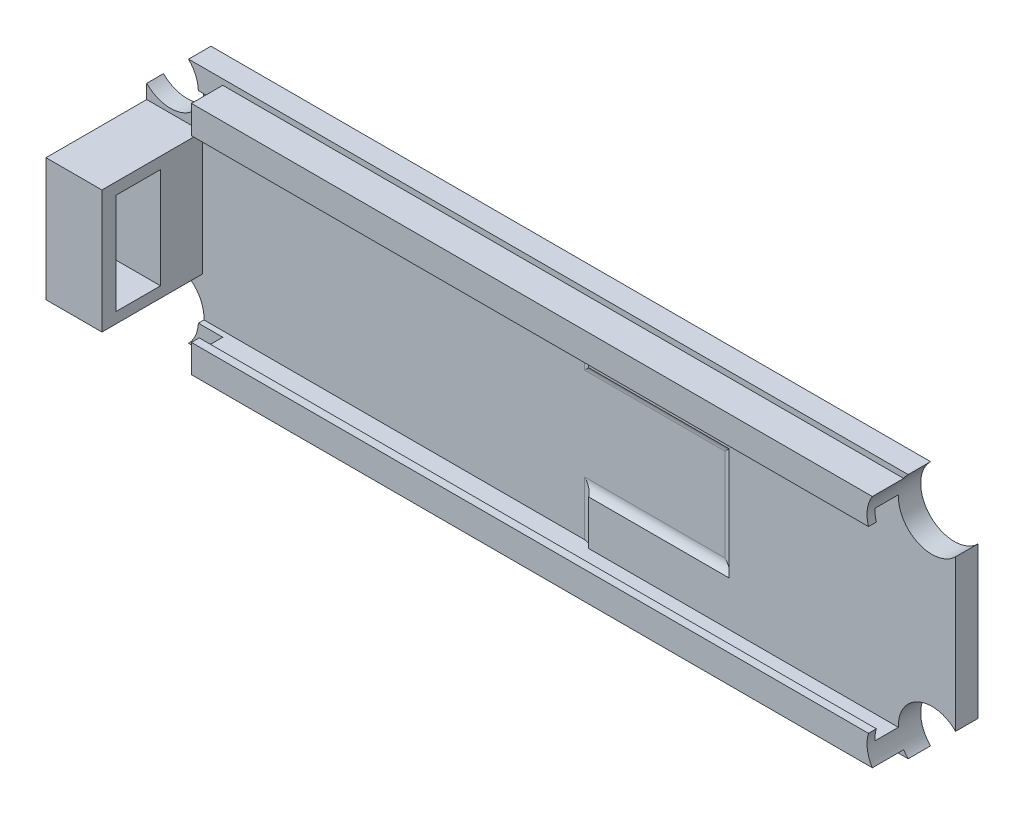
SolidWorks part; units mm, degrees
ref_plane "Ebene vorne" through (0, 0, 0) normal (1, 0, 0) x (0, 1, 0)
ref_plane "Ebene oben" through (0, 0, 0) normal (0, 0, 1) x (0, 1, 0)
ref_plane "Ebene rechts" through (0, 0, 0) normal (0, 1, 0) x (-1, 0, 0)
sketch "Skizze1" plane through (0, 0, 0) normal (0, 0, 1) x (0, 1, 0)
  line L30 (-11, -36.4) -> (11, -36.4)
  line L31 (-11, -36.4) -> (-11, 36.4)
  line L32 (-11, 36.4) -> (11, 36.4)
  line L33 (11, -36.4) -> (11, 36.4)
  line L34 (-11, -36.4) -> (11, 36.4) construction
  line L35 (-11, 36.4) -> (11, -36.4) construction
  point P0 (0, 0)
  dimension "D1" = 22
  dimension "D2" = 72.8
extrude "Aufsatz-Linear austragen1" add sketch "Skizze1" along normal blind 2
sketch "Skizze2" plane through (0, 0, 2) normal (0, 0, 1) x (1, 0, 0)
  line L0 (36.4, 11) -> (-36.4, 11) construction
  circle A0 centre (-34.28, 8.88) radius 3
  circle A1 centre (-34.28, -8.88) radius 3
  circle A2 centre (34.28, -8.88) radius 3
  circle A3 centre (34.28, 8.88) radius 3
  dimension "D3" = 6
  dimension "D6" = 6
  dimension "D9" = 6
  dimension "D12" = 6
  dimension "D1" = 2.12
  dimension "D2" = 2.12
  dimension "D4" = 2.12
  dimension "D5" = 2.12
  dimension "D7" = 2.12
  dimension "D8" = 2.12
  dimension "D10" = 2.12
  dimension "D11" = 2.12
extrude "Schnitt-Linear austragen1" cut sketch "Skizze2" against normal blind 2
sketch "Skizze3" plane through (0, 0, 2) normal (0, 0, 1) x (1, 0, 0)
  line L0 (-36.4, 0) -> (36.4, 0) construction
  line L1 (36.4, -10.5) -> (-29.1, -10.5)
  line L2 (36.4, -10.5) -> (36.4, 10.5)
  line L3 (36.4, 10.5) -> (-29.1, 10.5)
  line L4 (-29.1, -10.5) -> (-29.1, 10.5)
  line L5 (-36.4, 6.7574) -> (-36.4, -6.7574) construction
  line L6 (36.4, -6.7574) -> (36.4, 6.7574) construction
  dimension "D1" = 65.5
  dimension "D2" = 21
extrude "Aufsatz-Linear austragen2" add sketch "Skizze3" along normal blind 2.8
sketch "Skizze4" plane through (-29.1, 0, 0) normal (-1, 0, 0) x (0, -1, 0)
  line L0 (0, 0) -> (0, 2) construction
  line L1 (-8, 4.8) -> (8, 4.8)
  line L2 (-6.7574, 2) -> (6.7574, 2) construction
  line L3 (0, 2) -> (0, 4.8) construction
  line L4 (-10.5, 4.8) -> (10.5, 4.8) construction
  line L15 (-9, 2) -> (9, 2)
  line L16 (-9, 2) -> (-9, 4.1)
  line L17 (-9, 4.1) -> (9, 4.1) construction
  line L18 (9, 2) -> (9, 4.1)
  line L19 (-9, 2) -> (9, 4.1) construction
  line L20 (-9, 4.1) -> (9, 2) construction
  line L21 (-10.5, 4.8) -> (10.5, 4.8) construction
  line L22 (-9, 4.1) -> (-8, 4.1)
  line L23 (-8, 4.1) -> (-8, 4.8)
  line L24 (8, 4.8) -> (8, 4.1)
  line L25 (8, 4.1) -> (9, 4.1)
  point P2 (0, 3.4)
  point P5 (0, 3.05)
  point P6 (0, 3.4)
  point P20 (0, 4.8)
  dimension "D1" = 18
  dimension "D2" = 2.1
  dimension "D3" = 16
extrude "Schnitt-Linear austragen2" cut sketch "Skizze4" against normal through all
sketch "Skizze5" plane through (0, 0, 2) normal (0, 0, -1) x (1, 0, 0)
  line L0 (36.4, -11) -> (36.4, 11) construction
  line L2 (36.4, 6.7574) -> (36.4, -6.7574) construction
  circle A1 centre (34.28, -8.88) radius 3
  circle A2 centre (34.28, 8.88) radius 3
  point P3 (36.4, 0)
  dimension "D4" = 6
  dimension "D7" = 6
  dimension "D1" = 22
  dimension "D2" = 2.12
  dimension "D3" = 2.12
  dimension "D5" = 2.12
  dimension "D6" = 2.12
extrude "Schnitt-Linear austragen4" cut sketch "Skizze5" against normal through all
sketch "Skizze6" plane through (-36.4, 0, 0) normal (-1, 0, 0) x (0, -1, 0)
  line L0 (-6.7574, 2) -> (6.7574, 2) construction
  line L1 (-9, 2.5) -> (9, 2.5)
  line L2 (-9, 2.5) -> (-9, 1.5)
  line L3 (-9, 1.5) -> (9, 1.5)
  line L4 (9, 2.5) -> (9, 1.5)
  line L5 (-9, 2.5) -> (9, 1.5) construction
  line L6 (-9, 1.5) -> (9, 2.5) construction
  point P0 (0, 2)
  dimension "D1" = 18
  dimension "D2" = 1
extrude "Schnitt-Linear austragen5" cut sketch "Skizze6" against normal blind 40
sketch "Skizze8" plane through (0, 0, 2) normal (0, 0, 1) x (1, 0, 0)
  line L0 (1.156, -8) -> (1.156, 8) construction
  line L1 (1.156, -5.0073) -> (16.156, -5.0073)
  line L2 (1.156, -5.0073) -> (1.156, 4.9927)
  line L3 (1.156, 4.9927) -> (16.156, 4.9927)
  line L4 (16.156, -5.0073) -> (16.156, 4.9927)
  line L5 (31.412, -8) -> (-29.1, -8) construction
  line L8 (31.412, 8) -> (-29.1, 8) construction
  dimension "D1" = 10
  dimension "D2" = 15
extrude "Schnitt-Linear austragen6" cut sketch "Skizze8" against normal blind 0.5
fillet "Verrundung3" radius 1 5 edges at (3.6, -7.0037, 1.5) (9.878, -5.0073, 1.5) (3.6, 6.9963, 1.5) (9.878, 4.9927, 1.5) (16.156, -0.0073, 1.5)
sketch "Skizze9" plane through (0, 0, 1.5) normal (0, 0, 1) x (1, 0, 0)
  line L0 (-36.4, 6.7574) -> (-36.4, -6.7574) construction
  line L5 (-31.4, 5.5) -> (-36.4, 5.5)
  line L6 (-31.4, 5.5) -> (-31.4, -5.5)
  line L7 (-31.4, -5.5) -> (-36.4, -5.5)
  line L8 (-36.4, 5.5) -> (-36.4, -5.5)
  line L9 (-31.4, 5.5) -> (-36.4, -5.5) construction
  line L10 (-31.4, -5.5) -> (-36.4, 5.5) construction
  line L11 (-36.4, -6.7574) -> (-36.4, 6.7574) construction
  point P0 (-33.9, 0)
  point P8 (-36.4, 0)
  dimension "D1" = 11
  dimension "D2" = 5
extrude "Aufsatz-Linear austragen3" add sketch "Skizze9" along normal blind 9
sketch "Skizze10" plane through (-36.4, 0, 0) normal (-1, 0, 0) x (0, -1, 0)
  line L1 (-4.4618, 5.2634) -> (4.5382, 5.2634)
  line L2 (-4.4618, 5.2634) -> (-4.4618, 9.2634)
  line L3 (-4.4618, 9.2634) -> (4.5382, 9.2634)
  line L4 (4.5382, 5.2634) -> (4.5382, 9.2634)
  line L5 (-4.4618, 5.2634) -> (4.5382, 9.2634) construction
  line L6 (-4.4618, 9.2634) -> (4.5382, 5.2634) construction
  point P0 (0.0382, 7.2634)
  dimension "D1" = 4
  dimension "D2" = 9
extrude "Schnitt-Linear austragen7" cut sketch "Skizze10" against normal through all
